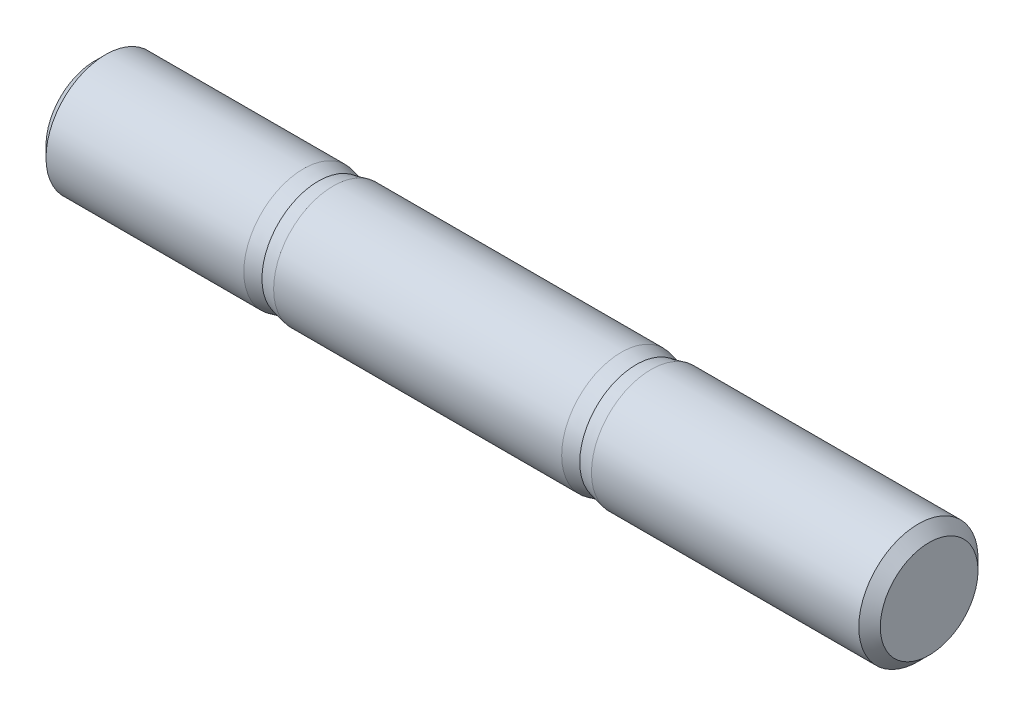
SolidWorks part; units mm, degrees
ref_plane "Front" through (0, 0, 0) normal (0, 0, 1) x (1, 0, 0)
ref_plane "Top" through (0, 0, 0) normal (0, 1, 0) x (1, 0, 0)
ref_plane "Right" through (0, 0, 0) normal (1, 0, 0) x (0, 0, -1)
sketch "Sketch1" plane through (0, 0, 0) normal (0, 0, 1) x (1, 0, 0)
  line L0 (-1.3108, 0) -> (30.3862, 0) construction
  line L1 (0, 0) -> (0, 3)
  line L2 (0, 3) -> (10.5, 3)
  line L3 (10.5, 3) -> (12, 2.675)
  line L4 (12, 2.675) -> (26.5, 2.675)
  line L5 (26.5, 2.675) -> (28, 3)
  line L6 (28, 3) -> (42, 3)
  line L7 (42, 3) -> (42, 0)
  line L8 (42, 0) -> (0, 0)
  dimension "D2" = 1.5
  dimension "l" = 30
  dimension "bm" = 12
  dimension "b" = 14
revolve "BaseHead" add sketch "Sketch1" angle 360 about L0
cosmetic thread "ThreadCosmetic1" [suppressed] parameters "D1"=10.5, "D2"=4.917
cosmetic thread "ThreadCosmetic2" [suppressed] parameters "b"=14, "D2"=4.917
chamfer "HeadChamfer" distance 0.5415 angle 45 2 edges at (42, 0, 3) (0, 0, 3)
sketch "Sketch2" plane through (0, 0, 0) normal (0, 0, 1) x (1, 0, 0)
  line L0 (-1.3108, 0) -> (31.2107, 0) construction
  line L2 (10.5, 2.675) -> (12, 3)
  line L3 (12, 3) -> (26.5, 3)
  line L4 (26.5, 3) -> (28, 2.675)
  line L7 (10.5, 3) -> (10.5, -3) construction
  line L9 (10.5, 2.675) -> (28, 2.675)
  line L10 (28, 3) -> (28, -3) construction
  dimension "D2" = 6
  dimension "D1" = 1.5
revolve "BaseBody" add sketch "Sketch2" angle 360 about L0
sketch "Sketch3" plane through (0, 0, 0) normal (0, 0, 1) x (1, 0, 0)
  line L0 (41.4585, 2.531) -> (41.7292, 3)
  line L1 (41.7292, 3) -> (41.7292, 3.5)
  line L2 (41.7292, 3.5) -> (41.1877, 3.5)
  line L3 (41.1877, 3.5) -> (41.1877, 3)
  line L4 (41.1877, 3) -> (41.4585, 2.531)
  line L5 (0, 0) -> (53.3681, 0) construction
  line L6 (0, 2.4585) -> (0, -2.4585) construction
  line L7 (41.4585, 3) -> (41.4585, -3) construction
  dimension "D1" = 0.5
  dimension "D2" = 0.5415
  dimension "D3" = 60
  dimension "D4" = 60
  dimension "D5" = 6
revolve "Cut-Revolve10" [suppressed] cut sketch "Sketch3" angle 360 about L5
pattern_linear "LPattern10" [suppressed] count 22 spacing 0.6498 along (-1, 0, 0) of bodies 103
sketch "Sketch4" plane through (0, 0, 0) normal (0, 1, 0) x (1, 0, 0)
  line L0 (0.5415, 2.531) -> (0.8123, 3)
  line L1 (0.8123, 3) -> (0.8123, 3.5)
  line L2 (0.8123, 3.5) -> (0.2708, 3.5)
  line L3 (0.2708, 3.5) -> (0.2708, 3)
  line L4 (0.2708, 3) -> (0.5415, 2.531)
  line L5 (0, 0) -> (3.4199, 0) construction
  line L6 (0.5415, 3) -> (0.5415, -3) construction
  dimension "D4" = 60
  dimension "D5" = 6
  dimension "D1" = 60
  dimension "D2" = 0.5
  dimension "D3" = 0.5415
revolve "Cut-Revolve11" [suppressed] cut sketch "Sketch4" angle 360 about L5
pattern_linear "LPattern11" [suppressed] count 16 spacing 0.6498 along (1, 0, 0) of bodies 105
equation "\"D2@Sketch1\" = \"X@Sketch1\""
equation "\"D2@ThreadCosmetic2\" = \"D2@ThreadCosmetic1\""
equation "\"D1@ThreadCosmetic1\" = \"bm@Sketch1\"-\"X@Sketch1\""
equation "\"b@ThreadCosmetic2\" = \"b@Sketch1\""
equation "\"D1@Sketch2\" = \"X@Sketch1\""
equation "\"D2@Sketch2\" = \"d@Sketch1\""
equation "\"D1@HeadChamfer\" =  (\"d@Sketch1\" - \"D2@ThreadCosmetic1\" )  / 2"
equation "\"D5@Sketch3\" = \"d@Sketch1\""
equation "\"D2@Sketch3\" =  ( \"d@Sketch1\" - \"D2@ThreadCosmetic2\" )  / 2"
equation "\"D3@LPattern10\" = \"D2@Sketch3\" * 1.2"
equation "\"D1@LPattern10\" = \"b@ThreadCosmetic2\" / \"D3@LPattern10\""
equation "\"D5@Sketch4\" = \"d@Sketch1\""
equation "\"D3@Sketch4\" = (  \"d@Sketch1\" - \"D2@ThreadCosmetic1\" )  / 2"
equation "\"D3@LPattern11\" = \"D3@Sketch4\" * 1.2"
equation "\"D1@LPattern11\" = \"D1@ThreadCosmetic1\" / \"D3@LPattern11\""
